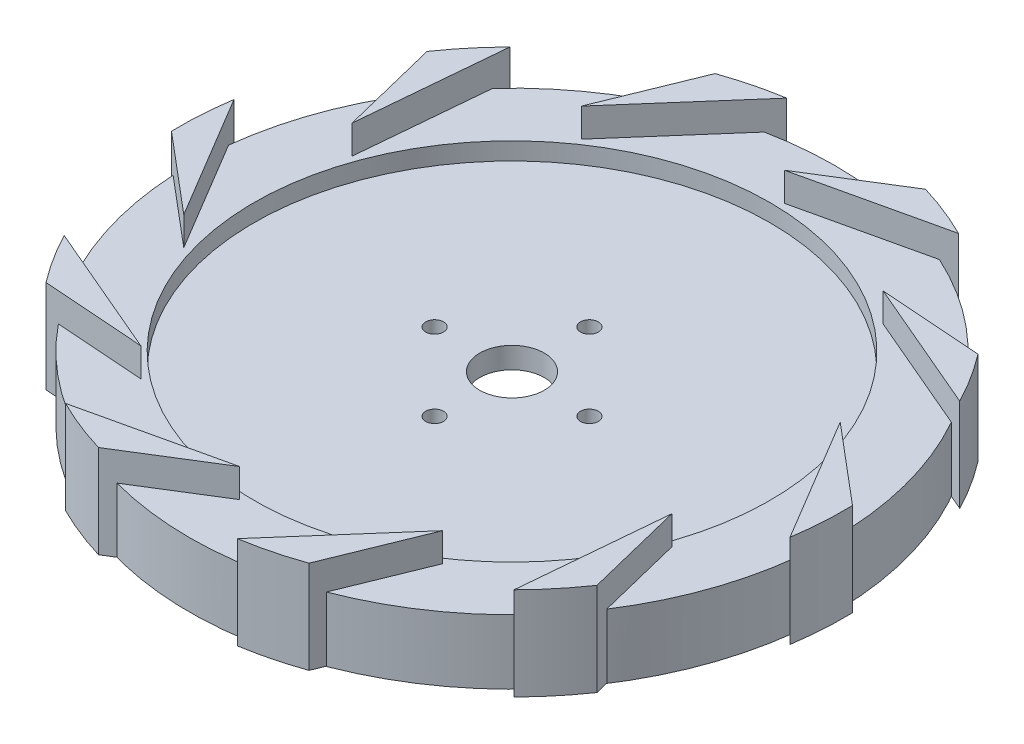
SolidWorks part; units mm, degrees
ref_plane "Front Plane" through (0, 0, 0) normal (0, 0, 1) x (1, 0, 0)
ref_plane "Top Plane" through (0, 0, 0) normal (0, 1, 0) x (1, 0, 0)
ref_plane "Right Plane" through (0, 0, 0) normal (1, 0, 0) x (0, 0, -1)
sketch "Sketch3" plane through (0, 0, 0) normal (0, 0, 1) x (1, 0, 0)
  line L0 (0, 0) -> (0, 40.1505) construction
  line L1 (-63.5, 16.0734) -> (-50.8, 16.0734)
  line L2 (-50.8, 16.0734) -> (-50.8, 12.6339)
  line L3 (-50.8, 12.6339) -> (0, 12.6339)
  line L4 (0, 12.6339) -> (0, 3.3734)
  line L5 (0, 3.3734) -> (-63.5, 3.3734)
  line L6 (-63.5, 3.3734) -> (-63.5, 16.0734)
  dimension "D1" = 12.7
  dimension "D2" = 63.5
  dimension "D3" = 50.8
revolve "Body" add sketch "Sketch3" angle 360 about L0
sketch "Sketch4" plane through (0, 0, 0) normal (0, 1, 0) x (1, 0, 0)
  line L0 (1.5533, 52.0769) -> (18.687, 62.7276)
  line L2 (29.4601, 58.4471) -> (1.5533, 52.0769)
  arc A0 (18.687, 62.7276) -> (29.4601, 58.4471) centre (0, 0) cw
extrude "Guide Vanes" add sketch "Sketch4" along direction (0, 1, 0) on the side of the normal blind 15.748 and the other way blind 2.54 from offset 5.969
pattern_circular "CirPattern4" count 10 over 360 about axis through (0, 16.0734, 0) along (0, -1, 0) of "Guide Vanes"
sketch "Sketch5" plane through (0, 3.3734, 0) normal (0, -1, 0) x (1, 0, 0)
  circle A0 centre (0, 0) radius 60.325
  dimension "D1" = 120.65
extrude "Hollow out" cut sketch "Sketch5" against normal blind 5.08 contours A0
sketch "Sketch6" plane through (0, 12.6339, 0) normal (0, 1, 0) x (1, 0, 0)
  circle A0 centre (0, 0) radius 6.35
  dimension "D1" = 12.7
extrude "Cut-Extrude1" cut sketch "Sketch6" against normal through all
sketch "Sketch7" plane through (0, 12.6339, 0) normal (0, 1, 0) x (1, 0, 0)
  circle A0 centre (0, 15.24) radius 1.7526
  circle A1 centre (0, 0) radius 6.35 construction
  dimension "D1" = 3.5052
  dimension "D2" = 15.24
extrude "Cut-Extrude2" cut sketch "Sketch7" against normal through all
pattern_circular "CirPattern5" count 4 over 360 about axis through (0, 12.6339, 0) along (0, 1, 0) of "Cut-Extrude2"
